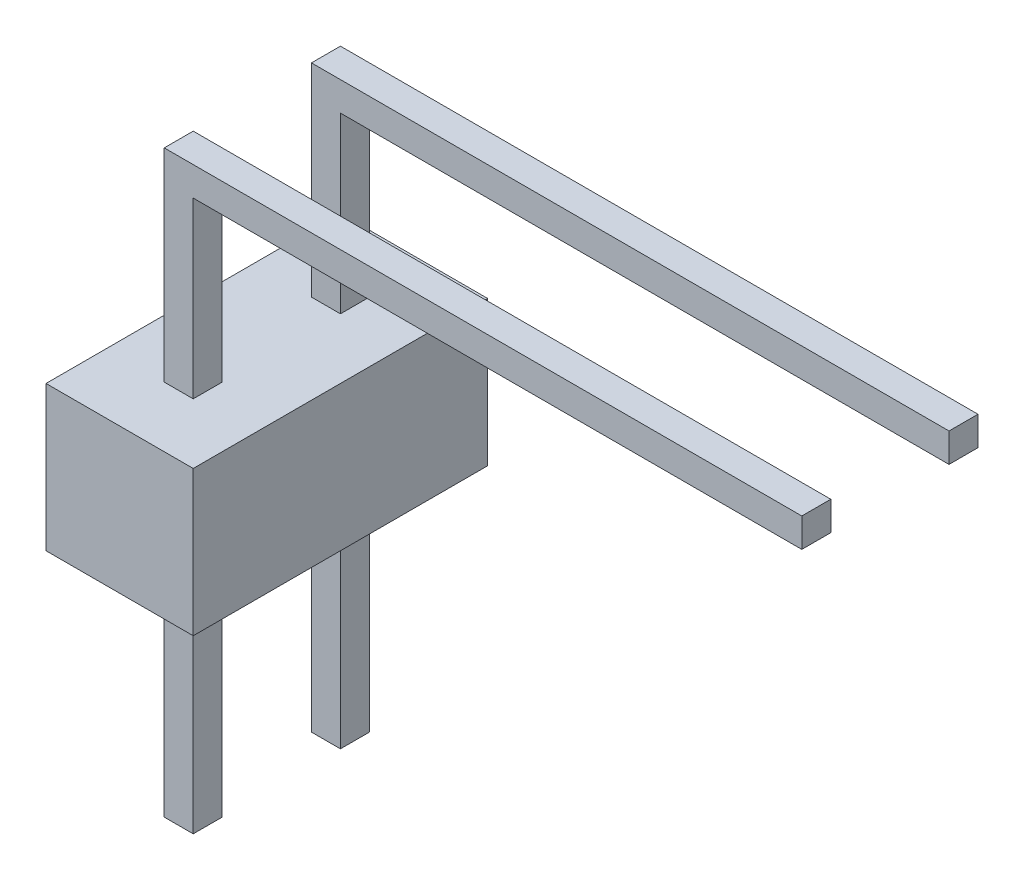
SolidWorks part; units mm, degrees
ref_plane "Plan de face" through (0, 0, 0) normal (0, 0, 1) x (1, 0, 0)
ref_plane "Plan de dessus" through (0, 0, 0) normal (0, 1, 0) x (1, 0, 0)
ref_plane "Plan de droite" through (0, 0, 0) normal (1, 0, 0) x (0, 0, -1)
sketch "Esquisse1" plane through (0, 0, 0) normal (0, 0, 1) x (1, 0, 0)
  line L0 (0, -4) -> (0, 6)
  line L1 (0, 6) -> (11, 6)
  line L2 (11, 6) -> (11, 5.5)
  line L3 (11, 5.5) -> (0.5, 5.5)
  line L4 (0.5, 5.5) -> (0.5, -4)
  line L5 (0.5, -4) -> (0, -4)
  dimension "D1" = 10
  dimension "D2" = 0.5
  dimension "D3" = 0.5
  dimension "D4" = 4
  dimension "D5" = 11
extrude "Boss.-Extru.1" add sketch "Esquisse1" along normal blind 0.5
sketch "Esquisse2" plane through (0, 0, 0) normal (0, 1, 0) x (1, 0, 0)
  line L0 (11, 0) -> (0, 0) construction
  line L1 (-1, 1) -> (1.54, 1)
  line L2 (-1, 1) -> (-1, -1.54)
  line L3 (-1, -1.54) -> (1.54, -1.54)
  line L4 (1.54, 1) -> (1.54, -1.54)
  line L5 (0, -0.5) -> (0, 0) construction
  dimension "D1" = 2.54
  dimension "D2" = 1
  dimension "D3" = 1
extrude "Boss.-Extru.2" add sketch "Esquisse2" along normal blind 2.5
ref_axis "Axe1" through (0, 0, 5.9906) along (0, 0, -1)
pattern_linear "Répétition linéaire3" count 2 spacing 2.54 along (0, 0, 1) of "Boss.-Extru.1", "Boss.-Extru.2"
